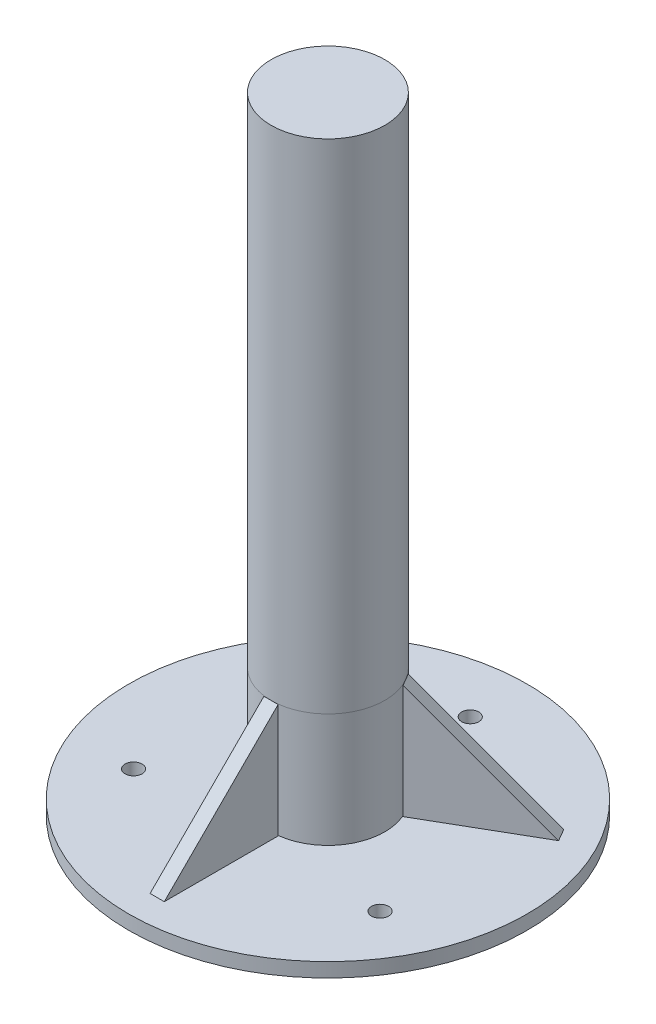
SolidWorks part; units mm, degrees
ref_plane "Front Plane" through (0, 0, 0) normal (0, 0, 1) x (1, 0, 0)
ref_plane "Top Plane" through (0, 0, 0) normal (0, 1, 0) x (1, 0, 0)
ref_plane "Right Plane" through (0, 0, 0) normal (1, 0, 0) x (0, 0, -1)
sketch "Sketch1" plane through (0, 0, 0) normal (0, 1, 0) x (1, 0, 0)
  circle A0 centre (0, 0) radius 70
  dimension "D1" = 140
extrude "Boss-Extrude1" add sketch "Sketch1" against normal blind 5
sketch "Sketch2" plane through (0, 0, 0) normal (0, 1, 0) x (1, 0, 0)
  circle A0 centre (0, 0) radius 20
  dimension "D1" = 40
extrude "Boss-Extrude2" add sketch "Sketch2" along normal blind 40 separate body
sketch "Sketch3" plane through (0, 40, 0) normal (0, 1, 0) x (1, 0, 0)
  circle A0 centre (0, 0) radius 20 construction
  circle A1 centre (0, 0) radius 20
extrude "Boss-Extrude3" add sketch "Sketch3" along normal blind 175 separate body
sketch "Sketch4" plane through (0, 0, 0) normal (1, 0, 0) x (0, 0, -1)
  line L0 (-60, 0) -> (-20, 0)
  line L1 (-20, 0) -> (-20, 40)
  line L2 (-20, 40) -> (-60, 0)
  line L3 (70, 0) -> (-70, 0) construction
  line L4 (-20, 40) -> (-20, 0) construction
  dimension "D1" = 40
  dimension "D2" = 45
  dimension "D3" = 0
  dimension "D4" = 0
extrude "Boss-Extrude4" add sketch "Sketch4" along normal blind 2.5 and the other way blind 2.5 separate body
pattern_circular "CirPattern1" count 3 every 120 about axis through (0, 40, 0) along (0, -1, 0) of "Boss-Extrude4"
sketch "Sketch5" plane through (0, 0, 0) normal (0, 1, 0) x (1, 0, 0)
  circle A0 centre (0, 50) radius 3
  circle A1 centre (43.3013, -25) radius 3
  circle A2 centre (-43.3013, -25) radius 3
  point P9 (0, 0)
  dimension "D1" = 6
  dimension "D2" = 50
  dimension "D3" = 3
extrude "Cut-Extrude1" cut sketch "Sketch5" against normal through all
